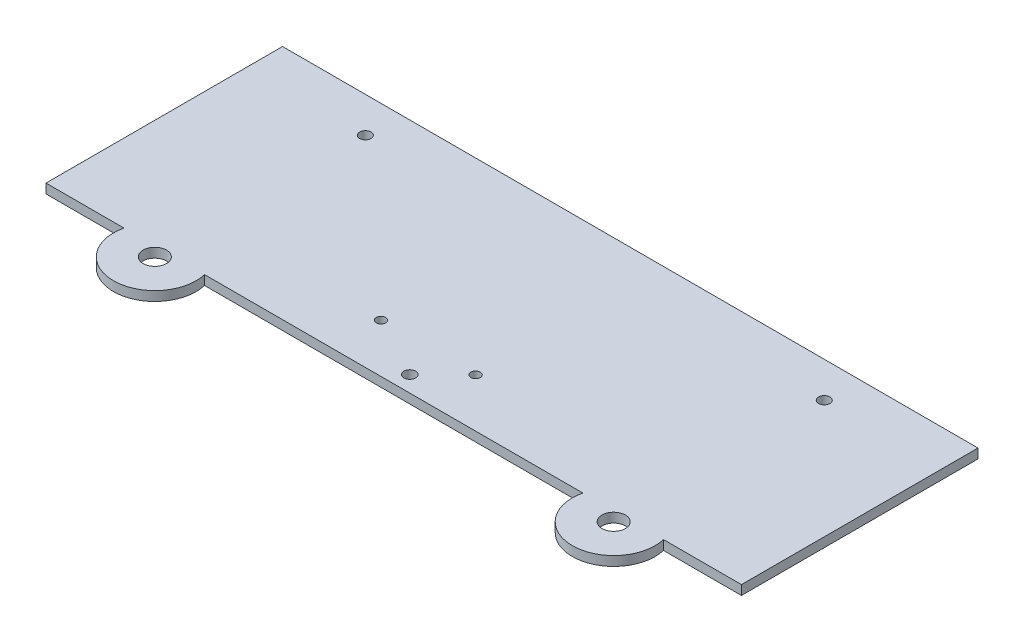
SolidWorks part; units mm, degrees
ref_plane "Front Plane" through (0, 0, 0) normal (0, 0, 1) x (1, 0, 0)
ref_plane "Top Plane" through (0, 0, 0) normal (0, 1, 0) x (1, 0, 0)
ref_plane "Right Plane" through (0, 0, 0) normal (1, 0, 0) x (0, 0, -1)
sketch "Sketch1" plane through (0, 0, 0) normal (0, 1, 0) x (1, 0, 0)
  line L0 (0, 0) -> (0, -63.5) construction
  line L1 (-186.69, -63.5) -> (186.69, -63.5)
  line L2 (-186.69, -63.5) -> (-186.69, 63.5)
  line L3 (-186.69, 63.5) -> (186.69, 63.5)
  line L4 (186.69, -63.5) -> (186.69, 63.5)
  line L5 (-186.69, -63.5) -> (186.69, 63.5) construction
  line L6 (-186.69, 63.5) -> (186.69, -63.5) construction
  line L7 (-123.19, -68.58) -> (-123.19, -63.5) construction
  line L8 (123.19, -68.58) -> (123.19, -63.5) construction
  line L9 (17.78, -37.338) -> (17.78, -63.5) construction
  circle A0 centre (-123.19, -68.58) radius 22.225
  circle A1 centre (123.19, -68.58) radius 22.225
  circle A2 centre (-123.19, -68.58) radius 6.2865
  circle A3 centre (123.19, -68.58) radius 6.2865
  circle A4 centre (-123.19, 44.45) radius 3.048
  circle A5 centre (123.19, 44.45) radius 3.048
  circle A6 centre (-33.02, -37.338) radius 2.54
  circle A7 centre (17.78, -37.338) radius 2.54
  circle A8 centre (0, -54.864) radius 3.175
  point P0 (0, 0)
  point P17 (123.19, 44.45)
  point P21 (-123.19, 44.45)
  dimension "D3" = 44.45
  dimension "D4" = 44.45
  dimension "D8" = 12.573
  dimension "D9" = 12.573
  dimension "D11" = 6.096
  dimension "D12" = 6.096
  dimension "D16" = 5.08
  dimension "D17" = 5.08
  dimension "D20" = 6.35
  dimension "D1" = 373.38
  dimension "D2" = 127
  dimension "D5" = 5.08
  dimension "D6" = 123.19
  dimension "D7" = 123.19
  dimension "D10" = 107.95
  dimension "D13" = 26.162
  dimension "D15" = 50.8
  dimension "D18" = 8.636
  dimension "D19" = 17.78
extrude "Boss-Extrude1" add sketch "Sketch1" along normal blind 5.0749 contours L1 A0 | L1 A1 | L3 L4 L1 L2 | A2 | A3 region at (-123.19, 0, 76.2008) region at (123.19, 0, 76.2008)
extrude "Cut-Extrude1" cut sketch "Sketch1<5>" along normal through all contours A3 | A2
sketch "Sketch1<5>" plane through (0, 0, 0) normal (0, 1, 0) x (1, 0, 0) same geometry as "Sketch1"
extrude "Cut-Extrude2" cut sketch "Sketch1<7>" along normal through all and the other way through all contours A4 | A5
sketch "Sketch1<7>" plane through (0, 0, 0) normal (0, 1, 0) x (1, 0, 0) same geometry as "Sketch1"
extrude "Cut-Extrude3" cut sketch "Sketch1<8>" along normal through all contours A7 | A6 | A8
sketch "Sketch1<8>" plane through (0, 0, 0) normal (0, 1, 0) x (1, 0, 0) same geometry as "Sketch1"
